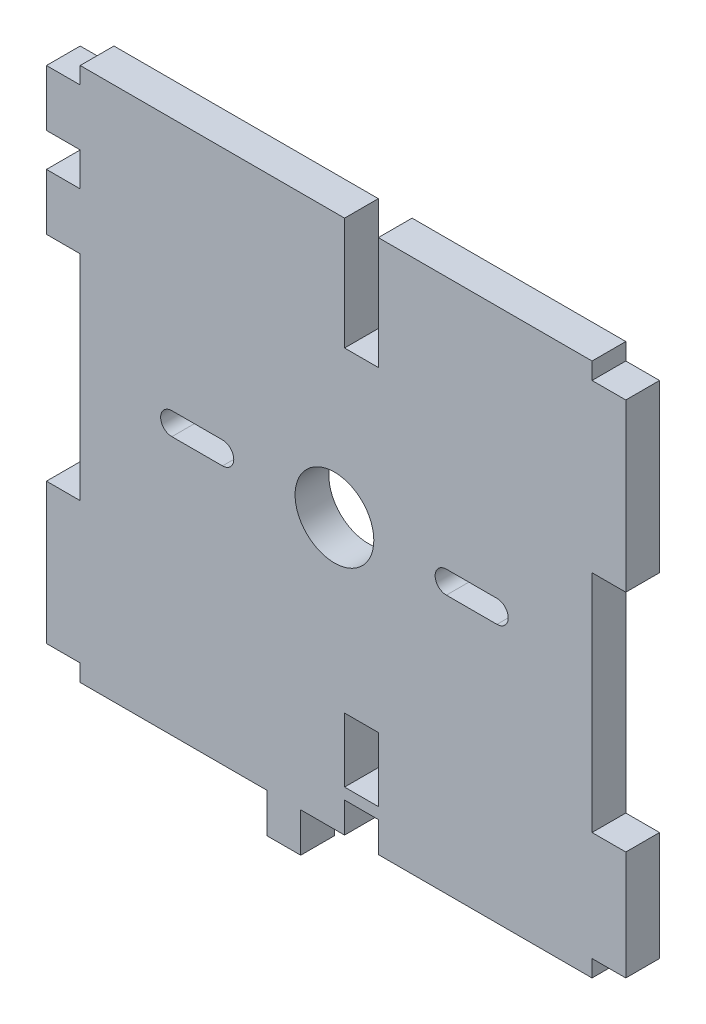
SolidWorks part; units mm, degrees
ref_plane "Plan de face" through (0, 0, 0) normal (0, 0, 1) x (1, 0, 0)
ref_plane "Plan de dessus" through (0, 0, 0) normal (0, 1, 0) x (1, 0, 0)
ref_plane "Plan de droite" through (0, 0, 0) normal (1, 0, 0) x (0, 0, -1)
sketch "Esquisse1" plane through (0, 0, 0) normal (0, 0, 1) x (1, 0, 0)
  line L0 (29.5, 47.5) -> (29.5, 37.5)
  line L1 (0, 0) -> (51.5, 0) construction
  line L2 (0, 0) -> (0, 47.5) construction
  line L3 (0, 47.5) -> (51.5, 47.5) construction
  line L4 (51.5, 0) -> (51.5, 47.5) construction
  line L5 (29.5, 37.5) -> (26.5, 37.5)
  line L6 (26.5, 37.5) -> (26.5, 47.5)
  line L7 (51.5, 46) -> (48.5, 46)
  line L8 (48.5, 46) -> (48.5, 47.5)
  line L9 (51.5, 31.2) -> (48.5, 31.2)
  line L10 (48.5, 31.2) -> (48.5, 11.2)
  line L11 (48.5, 11.2) -> (51.5, 11.2)
  line L12 (51.5, 1.5) -> (48.5, 1.5)
  line L13 (48.5, 1.5) -> (48.5, 0)
  line L14 (35.55, 24) -> (40.05, 24) construction
  line L15 (35.55, 25) -> (40.05, 25)
  line L16 (35.55, 23) -> (40.05, 23)
  line L17 (11.15, 24) -> (15.65, 24) construction
  line L18 (11.15, 25) -> (15.65, 25)
  line L19 (11.15, 23) -> (15.65, 23)
  line L20 (37.8, 24) -> (13.4, 24) construction
  line L21 (3, 47.5) -> (3, 46)
  line L22 (3, 46) -> (0, 46)
  line L23 (0, 41) -> (3, 41)
  line L24 (3, 41) -> (3, 38)
  line L25 (3, 38) -> (0, 38)
  line L26 (0, 33) -> (3, 33)
  line L27 (3, 33) -> (3, 14)
  line L28 (3, 14) -> (0, 14)
  line L29 (0, 1.5) -> (3, 1.5)
  line L30 (3, 1.5) -> (3, 0)
  line L31 (19.6, 0) -> (19.6, -3.5)
  line L32 (19.6, -3.5) -> (22.6, -3.5)
  line L33 (22.6, -3.5) -> (22.6, 0)
  line L34 (26.5, 0) -> (26.5, 2.7)
  line L35 (26.5, 2.7) -> (29.5, 2.7)
  line L36 (29.5, 2.7) -> (29.5, 0)
  line L37 (26.5, 37.5) -> (26.5, -6.1716) construction
  line L38 (26.5, 9.4) -> (29.5, 9.4)
  line L39 (26.5, 9.4) -> (26.5, 3.6978)
  line L40 (26.5, 3.6978) -> (29.5, 3.6978)
  line L41 (29.5, 9.4) -> (29.5, 3.6978)
  line L42 (29.5, 37.5) -> (29.5, -8.8826) construction
  line L43 (26.5, 47.5) -> (3, 47.5)
  line L44 (29.5, 47.5) -> (48.5, 47.5)
  line L45 (51.5, 46) -> (51.5, 31.2)
  line L46 (51.5, 11.2) -> (51.5, 1.5)
  line L47 (29.5, 0) -> (48.5, 0)
  line L48 (26.5, 0) -> (22.6, 0)
  line L49 (19.6, 0) -> (3, 0)
  line L50 (0, 1.5) -> (0, 14)
  line L51 (0, 33) -> (0, 38)
  line L52 (0, 41) -> (0, 46)
  circle A0 centre (25.6, 24) radius 3.5
  arc A1 (35.55, 25) -> (35.55, 23) centre (35.55, 24) ccw
  arc A2 (40.05, 23) -> (40.05, 25) centre (40.05, 24) ccw
  arc A3 (11.15, 25) -> (11.15, 23) centre (11.15, 24) ccw
  arc A4 (15.65, 23) -> (15.65, 25) centre (15.65, 24) ccw
  point P23 (37.8, 24)
  point P30 (13.4, 24)
  point P63 (1.5, 41)
  dimension "D13" = 7
  dimension "D15" = 19.4
  dimension "D16" = 6.5
  dimension "D20" = 5.45
  dimension "D21" = 5.45
  dimension "D23" = 1
  dimension "D24" = 6.5
  dimension "D1" = 51.5
  dimension "D2" = 47.5
  dimension "D3" = 22
  dimension "D4" = 3
  dimension "D5" = 10
  dimension "D6" = 3
  dimension "D7" = 1.5
  dimension "D8" = 14.8
  dimension "D9" = 20
  dimension "D10" = 3
  dimension "D11" = 1.5
  dimension "D12" = 3
  dimension "D14" = 20
  dimension "D17" = 2
  dimension "D18" = 23
  dimension "D19" = 7.45
  dimension "D22" = 2
  dimension "D25" = 3
  dimension "D26" = 1.5
  dimension "D27" = 5
  dimension "D28" = 3
  dimension "D29" = 5
  dimension "D30" = 3
  dimension "D31" = 3
  dimension "D32" = 19
  dimension "D33" = 1.5
  dimension "D34" = 3
  dimension "D35" = 3.5
  dimension "D36" = 3
  dimension "D37" = 22.6
  dimension "D38" = 9.4
  dimension "D39" = 2.7
  dimension "D40" = 0.9978
base flange "Tôle de base pliée1" sketch "Esquisse1" thickness 3 reverse thickness direction no parameters "D1"=1.5
sketch "Lignes de pliage1" [suppressed] plane through (0, 0, 0) normal (0, 1, 0) x (1, 0, 0)
sketch "Cube de visualisation1" [suppressed] plane through (0, 0, 0) normal (0, 1, 0) x (1, 0, 0)
sheet metal parameters "Tôlerie1" thickness 3 parameters "D1"=1.5
flat pattern "Etat déplié1" [suppressed]
sketch "Lignes de pliage2" plane through (0, 0, 0) normal (0, 1, 0) x (1, 0, 0)
sketch3d "Cube de visualisation2" [suppressed]
  line L0 (0, -3.5, 0) -> (51.5, -3.5, 0) construction
  line L1 (0, 47.5, 0) -> (51.5, 47.5, 0) construction
  line L2 (0, -3.5, 0) -> (0, 47.5, 0) construction
  line L3 (51.5, -3.5, 0) -> (51.5, 47.5, 0) construction
